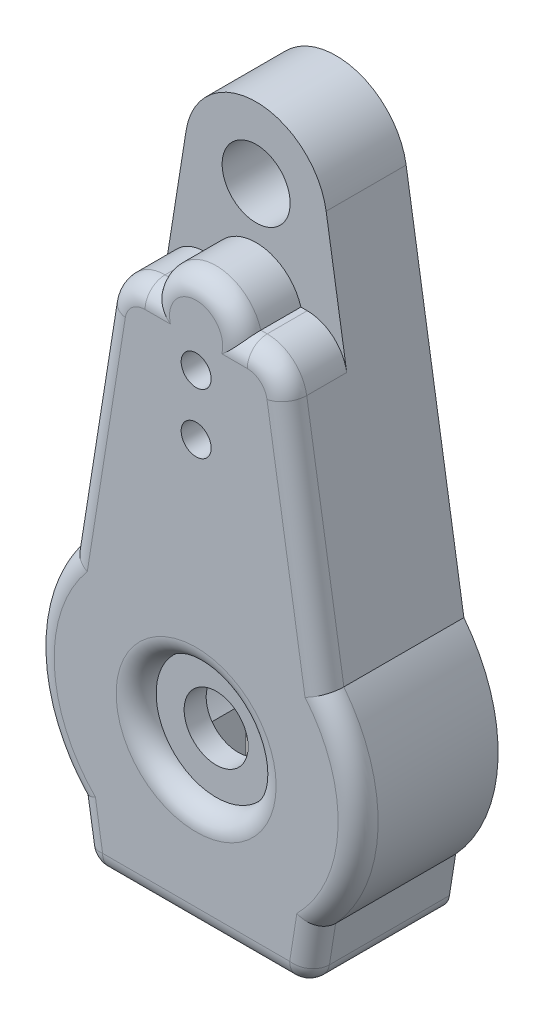
SolidWorks part; units mm, degrees
material "PLA 100% Infill"
ref_plane "Front Plane" through (0, 0, 0) normal (0, 0, 1) x (1, 0, 0)
ref_plane "Top Plane" through (0, 0, 0) normal (0, 1, 0) x (1, 0, 0)
ref_plane "Right Plane" through (0, 0, 0) normal (1, 0, 0) x (0, 0, -1)
sketch "Sketch1" plane through (0, 0, 0) normal (0, 0, 1) x (1, 0, 0)
  line L2 (-4.2619, 18.3531) -> (4.2619, 18.3531)
  line L3 (-2.469, 16.8925) -> (-2.2368, 18.3531) construction
  line L9 (2.469, 16.8925) -> (2.2368, 18.3531) construction
  line L10 (-4.5, 4.1183) -> (-4.5, 10.6021)
  line L11 (-4.5, 10.6021) -> (-3.4691, 10.6021) construction
  line L14 (0, -8.2602) -> (0, 19) construction
  line L15 (6.3881, 4.9802) -> (4.4442, 17.2066)
  line L16 (6.3881, 4.9802) -> (4.4442, 17.2066)
  line L17 (5.9754, -5.4685) -> (5.5315, -8.2602)
  line L18 (5.5315, -8.2602) -> (-5.5315, -8.2602)
  line L19 (2.469, -16.8925) -> (4.5, -4.1183) construction
  line L20 (4.4442, 17.2066) -> (3.5013, 23.1367)
  line L21 (0, 19) -> (0, 33.2339) construction
  line L22 (-4.4442, 17.2066) -> (-3.5013, 23.1367)
  line L23 (-6.3881, 4.9802) -> (-4.4442, 17.2066)
  line L24 (-5.9754, -5.4685) -> (-5.5315, -8.2602)
  line L25 (2.469, 16.8925) -> (4.5, 4.1183) construction
  line L26 (-2.469, 16.8925) -> (-4.5, 4.1183) construction
  line L27 (-2.469, -16.8925) -> (-4.5, -4.1183) construction
  line L28 (3.8415, -8.2602) -> (4.5, -4.1183) construction
  line L29 (2.469, 16.8925) -> (4.5, 4.1183) construction
  line L30 (-2.469, 16.8925) -> (-4.5, 4.1183) construction
  line L31 (-3.8415, -8.2602) -> (-4.5, -4.1183) construction
  line L32 (4.5, 10.6021) -> (4.5, 4.1183)
  line L33 (3.4691, 10.6021) -> (4.5, 10.6021) construction
  line L34 (-2.2368, 18.3531) -> (-4.5, 10.6021)
  line L35 (2.2368, 18.3531) -> (4.5, 10.6021)
  line L36 (-4.5, -4.1183) -> (-4.5, -8.2602)
  line L38 (4.5, -8.2602) -> (4.5, -4.1183)
  arc A2 (-5.9754, -5.4685) -> (-6.3881, 4.9802) centre (0, 0) cw
  arc A3 (2.2368, 18.3531) -> (-2.2368, 18.3531) centre (0, 17.7) ccw
  circle A6 centre (0, 0) radius 1.6
  arc A10 (3.5013, 23.1367) -> (-3.5013, 23.1367) centre (0, 22.58) ccw
  arc A13 (5.9754, -5.4685) -> (6.3881, 4.9802) centre (0, 0) ccw
  arc A14 (5.9754, -5.4685) -> (6.3881, 4.9802) centre (0, 0) ccw
  arc A15 (2.469, 16.8925) -> (-2.469, 16.8925) centre (0, 16.5) ccw construction
  circle A16 centre (0, 22.58) radius 1.7
  circle A17 centre (0, 16) radius 0.75 construction
  circle A18 centre (0, 13) radius 0.75 construction
  circle A19 centre (0, 10) radius 0.75 construction
  circle A20 centre (0, 7) radius 0.75 construction
  circle A21 centre (0, -7) radius 0.75 construction
  circle A22 centre (0, 16) radius 0.75
  circle A23 centre (0, 13) radius 0.75
  circle A24 centre (0, 10) radius 0.75
  circle A25 centre (0, 7) radius 0.75
  circle A26 centre (0, -7) radius 0.75
  arc A27 (4.5, -4.1183) -> (4.5, 4.1183) centre (0, 0) ccw construction
  arc A28 (-4.5, 4.1183) -> (-4.5, -4.1183) centre (0, 0) ccw construction
  arc A29 (4.5, -4.1183) -> (4.5, 4.1183) centre (0, 0) ccw
  arc A30 (2.469, 16.8925) -> (-2.469, 16.8925) centre (0, 16.5) ccw construction
  arc A31 (-4.5, 4.1183) -> (-4.5, -4.1183) centre (0, 0) ccw
  point P24 (0, -8.2602)
  point P58 (0, 0)
  point P59 (0, 0)
  arc M60 (4.5, -4.1183) -> (4.5, 4.1183) centre (0, 0) ccw
  line M61 (4.5, 4.1183) -> (2.469, 16.8925)
  arc M62 (2.469, 16.8925) -> (-2.469, 16.8925) centre (0, 16.5) ccw
  line M63 (-2.469, 16.8925) -> (-4.5, 4.1183)
  arc M64 (-4.5, 4.1183) -> (-4.5, -4.1183) centre (0, 0) ccw
  line M65 (-4.5, -4.1183) -> (-2.469, -16.8925)
  line M67 (2.469, -16.8925) -> (4.5, -4.1183)
  circle M68 centre (0, 0) radius 1.5
  circle M69 centre (0, 7) radius 0.75
  circle M70 centre (0, 10) radius 0.75
  circle M71 centre (0, 13) radius 0.75
  circle M72 centre (0, 16) radius 0.75
  circle M73 centre (0, -7) radius 0.75
  circle M74 centre (0, -10) radius 0.75
  dimension "D2" = 2
  dimension "D4" = 3.4
  dimension "D5" = 2.3302
  dimension "D6" = 22.58
  dimension "D8" = 3.2
  dimension "D1" = 2.8268
  dimension "D3" = 6.4838
extrude "Boss-Extrude4" add sketch "Sketch1" against normal blind 4 contours A30 L20 A10 L22 A16 | A31 L30 A30 L23 A2 L24 L18 L31 | A30 L29 A29 L28 L18 L17 A14 L16 region at (-3.7677, 20.7268, 0) region at (-5.4944, 4.5544, 0) region at (5.4944, 4.5544, 0)
extrude "Boss-Extrude6" add sketch "Sketch1<9>" along normal blind 3 and the other way blind 0.1 contours A2 L24 L18 L36 L10 L34 L2 L22 L23 M64 | L2 A3 | L35 L2 L34 L10 L32 M63 M62 M61 | L18 M67 M60 M61 M62 M63 M64 M65 M74 M68 M70 M72 M73 M71 M69 | L17 A14 L16 L20 L2 L35 L32 L38 L18 M60 | L18 L38 M67 | L36 L18 M65 | L35 L2 L32 M62 M61 | L2 M62 | A25 | A24 | A26 region at (-5.4944, 4.5544, 0) region at (0, 19.2108, 0) region at (-3.6924, 11.2543, 0) region at (0, 18.615, 0) region at (0, 3.4642, 0) region at (3.6924, 11.2543, 0) region at (5.4944, 4.5544, 0) region at (-4.2805, -6.8796, 0) region at (4.2805, -6.8796, 0)
sketch "Sketch1<9>" plane through (0, 0, 0) normal (0, 0, 1) x (1, 0, 0) same geometry as "Sketch1"
fillet "Fillet2" radius 1 12 edges at (5.5315, -8.2602, -0.5) (-5.5315, -8.2602, -0.5) (5.7535, -6.8644, 3) (8.0937, -0.3197, 3) (5.325, 11.6667, 3) (-5.7535, -6.8644, 3) (-8.0937, -0.3197, 3) (-5.325, 11.6667, 3) (3.2493, 18.3531, 3) (0, 20.0302, 3) (-3.2493, 18.3531, 3) (0, -8.2602, 3)
fillet "Fillet3" radius 2 4 edges at (4.0119, 18.0602, 2.7071) (-4.0119, 18.0602, 2.7071) (-4.2619, 18.3531, 1) (4.2619, 18.3531, 1)
sketch "Sketch2" plane through (0, 0, -0.1) normal (0, 0, -1) x (-1, 0, 0)
  circle A0 centre (0, 0) radius 4
  dimension "D1" = 8
extrude "Cut-Extrude1" cut sketch "Sketch2" against normal blind 1
sketch "Sketch3" plane through (0, 0, 3) normal (0, 0, 1) x (1, 0, 0)
  circle A0 centre (0, 0) radius 3
  dimension "D1" = 6
extrude "Cut-Extrude2" cut sketch "Sketch3" against normal blind 1
fillet "Fillet4" radius 1 1 edges at (-4, 0, 0.9)
fillet "Fillet5" radius 1 1 edges at (3, 0, 3)
